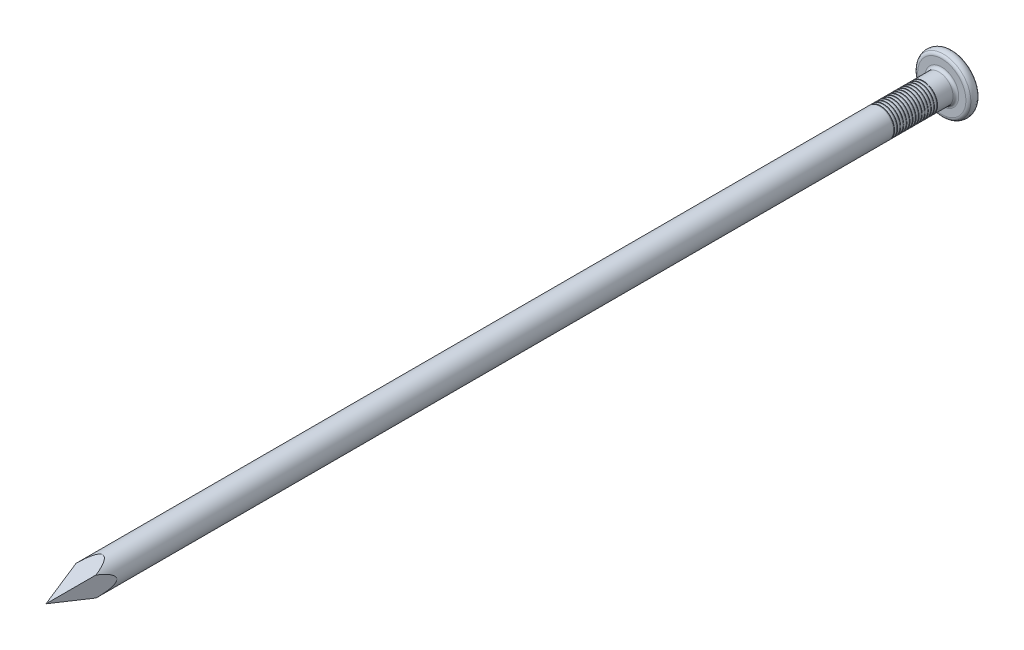
SolidWorks part; units mm, degrees
ref_plane "Front Plane" through (0, 0, 0) normal (0, 0, 1) x (1, 0, 0)
ref_plane "Top Plane" through (0, 0, 0) normal (0, 1, 0) x (1, 0, 0)
ref_plane "Right Plane" through (0, 0, 0) normal (1, 0, 0) x (0, 0, -1)
sketch "Sketch1" plane through (0, 0, 0) normal (1, 0, 0) x (0, 0, -1)
  line L0 (-152.4, 0) -> (152.4, 0) construction
  line L1 (-152.4, 4.7625) -> (-152.4, -4.7625) construction
  line L2 (152.4, -9.525) -> (152.4, 9.525) construction
  line L3 (0, 0) -> (0, 9.525) construction
  point P3 (101.6, 0)
  point P4 (0, 0)
  point P8 (-152.4, 0)
  point P10 (-101.6, 0)
  point P11 (152.4, 0)
  dimension "Length" = 304.8
  dimension "Shank Diameter" = 9.525
  dimension "Head Diameter" = 19.05
  dimension "D1" = 50.8
sketch "Sketch2" plane through (0, 0, 0) normal (1, 0, 0) x (0, 0, -1)
  line L1 (-133.35, -4.7625) -> (152.4, -4.7625)
  line L2 (-152.4, 0) -> (152.4, 0) construction
  line L3 (-152.4, 0) -> (152.4, 0)
  line L4 (152.4, 0) -> (152.4, -4.7625)
  line L5 (-152.4, 0) -> (-152.4, -4.7625)
  line L7 (-152.4, -4.7625) -> (-133.35, -4.7625)
  line L8 (-133.35, -4.7625) -> (-152.4, -0.0025) construction
  line L9 (152.4, -9.525) -> (152.4, 9.525) construction
  point P2 (144.4625, 0)
  dimension "D1" = 19.05
  dimension "D2" = 0.0025
  dimension "D3" = 7.9375
revolve "Revolve1" add sketch "Sketch2" angle 360 about L3
sketch "Sketch3" plane through (0, 0, 0) normal (1, 0, 0) x (0, 0, -1)
  line L0 (-152.4, -0.0025) -> (-133.35, -4.7625)
  line L1 (-133.35, -4.7625) -> (-152.4, -4.7625)
  line L2 (-152.4, -4.7625) -> (-152.4, -0.0025)
  line L3 (-152.4, 0) -> (152.4, 0) construction
  line L4 (-152.4, 0) -> (152.4, 0) construction
extrude "Cut-Extrude1" cut sketch "Sketch3" against normal through all both and the other way through all
pattern_circular "CirPattern1" count 4 over 360 about axis through (0, 0, -152.4) along (0, 0, 1) of "Cut-Extrude1"
sketch "Sketch5" plane through (0, 0, 0) normal (1, 0, 0) x (0, 0, -1)
  line L0 (152.4, -9.525) -> (152.4, 9.525) construction
  line L1 (152.4, 0) -> (152.4, 9.525) construction
  line L2 (148.8281, 9.525) -> (148.8281, 0) construction
  line L3 (-152.4, 0) -> (152.4, 0) construction
  line L5 (148.8281, 9.525) -> (152.4, 9.525) construction
  line L6 (152.4, 0) -> (0, 0) construction
  line L7 (148.8281, 0) -> (152.4, 0)
  line L8 (148.8281, 0) -> (148.8281, 8.105)
  line L9 (152.4, 0) -> (152.4, 8.105)
  arc A0 (149.4173, 9.1771) -> (151.8108, 9.1771) centre (150.6141, 7.2926) cw
  arc A1 (152.4, 8.105) -> (151.8108, 9.1771) centre (151.13, 8.105) ccw
  arc A2 (148.8281, 8.105) -> (149.4173, 9.1771) centre (150.0981, 8.105) cw
  point P2 (143.1925, 0)
  point P3 (-151.13, 0)
  point P12 (148.8281, 9.525)
  point P20 (152.4, 8.632)
  point P23 (148.8281, 8.632)
  dimension "D6" = 1.27
  dimension "D1" = 3.5719
  dimension "D2" = 1.27
  dimension "D4" = 294.3225
  dimension "D5" = 0.893
  dimension "D3" = 1.27
revolve "Revolve2" add sketch "Sketch5" angle 360 about L6 region at (0, 4.6206, -150.6141)
ref_plane "Plane1" through (4.7625, 0, 0) normal (1, 0, 0) x (0, 0, -1)
sketch "Sketch6" plane through (4.7625, 0, 0) normal (1, 0, 0) x (0, 0, -1)
  line L0 (-152.4, 0) -> (152.4, 0) construction
  line L1 (-152.4, 0) -> (152.4, 0) construction
  line L8 (140.2556, -9.525) -> (140.5731, -9.525)
  line L41 (142.3194, -9.525) -> (142.6369, -9.525)
  line L42 (142.3194, -9.525) -> (142.3194, 9.525)
  line L43 (142.3194, 9.525) -> (142.6369, 9.525)
  line L44 (142.6369, -9.525) -> (142.6369, 9.525)
  line L45 (142.3194, -9.525) -> (142.6369, 9.525) construction
  line L46 (142.3194, 9.525) -> (142.6369, -9.525) construction
  line L47 (141.2875, -9.525) -> (141.605, -9.525)
  line L48 (141.605, -9.525) -> (141.605, 9.525)
  line L49 (141.2875, -9.525) -> (141.2875, 9.525)
  line L50 (141.2875, 9.525) -> (141.605, 9.525)
  line L52 (140.5731, -9.525) -> (140.5731, 9.525)
  line L53 (140.2556, -9.525) -> (140.2556, 9.525)
  line L54 (140.2556, 9.525) -> (140.5731, 9.525)
  line L55 (139.2238, -9.525) -> (139.5413, -9.525)
  line L56 (139.5413, -9.525) -> (139.5413, 9.525)
  line L57 (139.2238, -9.525) -> (139.2238, 9.525)
  line L58 (139.2238, 9.525) -> (139.5413, 9.525)
  line L59 (138.1919, -9.525) -> (138.5094, -9.525)
  line L60 (138.5094, -9.525) -> (138.5094, 9.525)
  line L61 (138.1919, -9.525) -> (138.1919, 9.525)
  line L62 (138.1919, 9.525) -> (138.5094, 9.525)
  line L63 (137.16, -9.525) -> (137.4775, -9.525)
  line L64 (137.4775, -9.525) -> (137.4775, 9.525)
  line L65 (137.16, -9.525) -> (137.16, 9.525)
  line L66 (137.16, 9.525) -> (137.4775, 9.525)
  line L67 (136.1281, -9.525) -> (136.4456, -9.525)
  line L68 (136.4456, -9.525) -> (136.4456, 9.525)
  line L69 (136.1281, -9.525) -> (136.1281, 9.525)
  line L70 (136.1281, 9.525) -> (136.4456, 9.525)
  line L71 (135.0963, -9.525) -> (135.4138, -9.525)
  line L72 (135.4138, -9.525) -> (135.4138, 9.525)
  line L73 (135.0963, -9.525) -> (135.0963, 9.525)
  line L74 (135.0963, 9.525) -> (135.4138, 9.525)
  line L75 (134.0644, -9.525) -> (134.3819, -9.525)
  line L76 (134.3819, -9.525) -> (134.3819, 9.525)
  line L77 (134.0644, -9.525) -> (134.0644, 9.525)
  line L78 (134.0644, 9.525) -> (134.3819, 9.525)
  line L79 (133.0325, -9.525) -> (133.35, -9.525)
  line L80 (133.35, -9.525) -> (133.35, 9.525)
  line L81 (133.0325, -9.525) -> (133.0325, 9.525)
  line L82 (133.0325, 9.525) -> (133.35, 9.525)
  line L83 (132.0006, -9.525) -> (132.3181, -9.525)
  line L84 (132.3181, -9.525) -> (132.3181, 9.525)
  line L85 (132.0006, -9.525) -> (132.0006, 9.525)
  line L86 (132.0006, 9.525) -> (132.3181, 9.525)
  line L87 (130.9688, -9.525) -> (131.2863, -9.525)
  line L88 (131.2863, -9.525) -> (131.2863, 9.525)
  line L89 (130.9688, -9.525) -> (130.9688, 9.525)
  line L90 (130.9688, 9.525) -> (131.2863, 9.525)
  line L91 (148.8281, 8.105) -> (148.8281, -8.105) construction
  line L92 (148.8281, 9.525) -> (152.4, 9.525) construction
  line L93 (129.9369, -9.525) -> (130.2544, -9.525)
  line L94 (130.2544, -9.525) -> (130.2544, 9.525)
  line L95 (129.9369, -9.525) -> (129.9369, 9.525)
  line L96 (129.9369, 9.525) -> (130.2544, 9.525)
  line L97 (128.905, -9.525) -> (129.2225, -9.525)
  line L98 (129.2225, -9.525) -> (129.2225, 9.525)
  line L99 (128.905, -9.525) -> (128.905, 9.525)
  line L100 (128.905, 9.525) -> (129.2225, 9.525)
  line L101 (127.8731, -9.525) -> (128.1906, -9.525)
  line L102 (128.1906, -9.525) -> (128.1906, 9.525)
  line L103 (127.8731, -9.525) -> (127.8731, 9.525)
  line L104 (127.8731, 9.525) -> (128.1906, 9.525)
  point P15 (142.4781, 0)
  dimension "D7" = 0.7144
  dimension "D1" = 0.3175
  dimension "D5" = 6.35
  dimension "D6" = 15
extrude "Cut-Extrude3" cut sketch "Sketch6" against normal through all
sketch "Sketch7" plane through (0, 0, -148.8281) normal (0, 0, 1) x (1, 0, 0)
  circle A0 centre (0, 0) radius 4.6355
  circle A1 centre (0, 0) radius 4.7625 construction
  dimension "D1" = 0.127
extrude "Boss-Extrude1" add sketch "Sketch7" along normal up to vertex (148.8281 mm away) up to point (0, 0, 0)
fillet "Fillet1" radius 0.9525 1 edges at (-4.7625, 0, -148.8281)
equation "\"D1@Sketch2\"=\"Shank Diameter@Sketch1\"*2"
equation "\"D1@Sketch5\"=\"Head Diameter@Sketch1\" * 0.1875"
equation "\"D7@Sketch6\"=\"D1@Sketch6\"*2.25"
equation "\"D5@Sketch5\"=\"D1@Sketch5\"/4"
equation "\"D1@Fillet1\"=\"Head Diameter@Sketch1\"*0.05"
